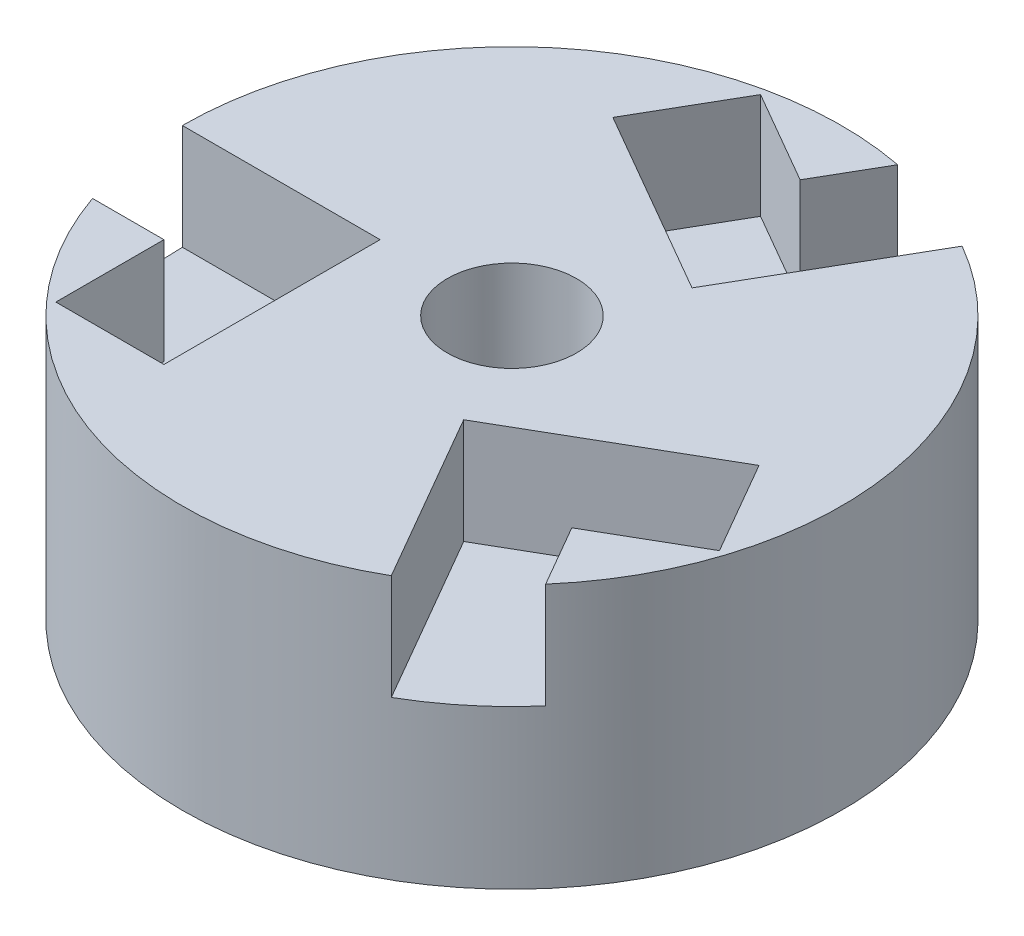
SolidWorks part; units mm, degrees
ref_plane "Front Plane" through (0, 0, 0) normal (0, 0, 1) x (1, 0, 0)
ref_plane "Top Plane" through (0, 0, 0) normal (0, 1, 0) x (1, 0, 0)
ref_plane "Right Plane" through (0, 0, 0) normal (1, 0, 0) x (0, 0, -1)
sketch "Sketch1" plane through (0, 0, 0) normal (0, 1, 0) x (1, 0, 0)
  circle A0 centre (0, 0) radius 25
  dimension "D1" = 50
extrude "Boss-Extrude1" add sketch "Sketch1" along normal blind 20
sketch "Sketch2" plane through (0, 20, 0) normal (0, 1, 0) x (1, 0, 0)
  line L0 (-25, 0) -> (-10, 0)
  line L1 (-10, 0) -> (-10, -16.4)
  line L2 (-10, -16.4) -> (-18.2, -16.4)
  line L3 (-18.2, -16.4) -> (-18.2, -8.2)
  line L4 (-18.2, -8.2) -> (-23.6169, -8.2)
  circle A0 centre (0, 0) radius 25 construction
  arc A1 (-25, 0) -> (-23.6169, -8.2) centre (0, 0) ccw
  dimension "D1" = 8.2
  dimension "D2" = 8.2
  dimension "D3" = 8.2
  dimension "D4" = 10
extrude "Cut-Extrude1" cut sketch "Sketch2" against normal blind 8
pattern_circular "CirPattern1" count 3 over 360 about axis through (0, 0, 0) along (0, -1, 0) of "Cut-Extrude1"
sketch "Sketch7" plane through (0, 0, 0) normal (0, -1, 0) x (1, 0, 0)
  circle A0 centre (0, 0) radius 15.1
  dimension "D1" = 30.2
extrude "Cut-Extrude3" cut sketch "Sketch7" against normal blind 8.7
sketch "Sketch8" plane through (0, 8.7, 0) normal (0, -1, 0) x (1, 0, 0)
  circle A0 centre (0, 0) radius 4.9
  dimension "D1" = 9.8
extrude "Cut-Extrude4" cut sketch "Sketch8" against normal through all
equation "\"D3@Sketch2\"=\"D1@Sketch2\""
equation "\"D2@Sketch2\"=\"D1@Sketch2\""
